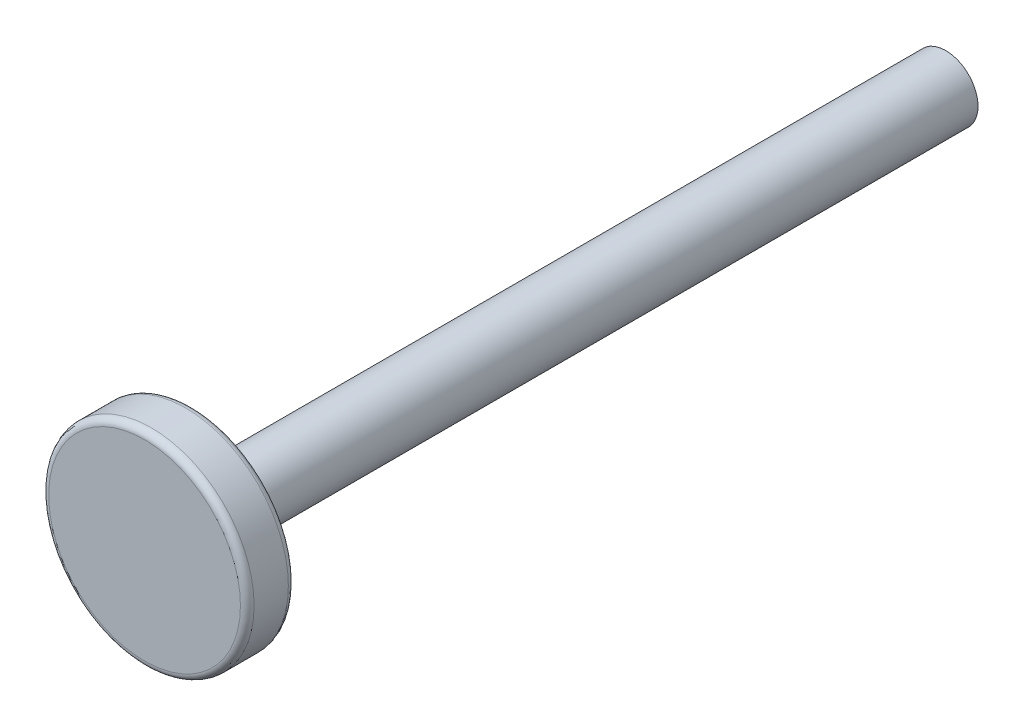
SolidWorks part; units mm, degrees
ref_plane "Front Plane" through (0, 0, 0) normal (0, 0, 1) x (1, 0, 0)
ref_plane "Top Plane" through (0, 0, 0) normal (0, 1, 0) x (1, 0, 0)
ref_plane "Right Plane" through (0, 0, 0) normal (1, 0, 0) x (0, 0, -1)
sketch "Sketch2" plane through (0, 0, 7.4325) normal (0, 0, 1) x (1, 0, 0)
  circle A0 centre (-105.394, 23.97) radius 2.35
  dimension "D1" = 4.7
extrude "Boss-Extrude1" add sketch "Sketch2" along normal blind 55
sketch "Sketch3" plane through (0, 0, 62.4325) normal (0, 0, 1) x (1, 0, 0)
  circle A0 centre (-105.394, 23.97) radius 7.5
  dimension "D1" = 15
extrude "Boss-Extrude2" add sketch "Sketch3" along normal blind 3.5
fillet "Fillet1" radius 0.5 3 edges at (-97.894, 23.97, 65.9325) (-97.894, 23.97, 62.4325) (-103.044, 23.97, 62.4325)
hole_wizard "M3x0.5 Tapped Hole1" positions "3DSketch1" profile "Sketch4" tap size "M3x0.5" standard "ANSI Metric"
sketch3d "3DSketch1"
  line L0 (-105.394, 23.97, 61.9325) -> (-105.394, 23.97, 7.4325) construction
  circle A0 centre (-105.394, 23.97, 7.4325) radius 1.9165
  point P0 (-105.394, 23.97, 7.4325)
  point P17 (-105.394, 23.97, 9.3491)
sketch "Sketch4" plane through (-105.394, 23.97, 7.4325) normal (1, 0, 0) x (0, 1, 0)
  line L0 (0, 0) -> (0, 20.7511)
  line L1 (0, 20.7511) -> (1.25, 20)
  line L2 (1.25, 20) -> (1.25, 0.275)
  line L3 (1.25, 0.275) -> (1.525, 0)
  line L5 (1.525, 0) -> (0, 0)
  line L6 (-1.25, 0.275) -> (-1.525, 0) construction
  line L10 (0, 20.7511) -> (-1.25, 20) construction
  line L11 (0, -6.35) -> (0, 107.95) construction
  dimension "Tap Drill Dia." = 2.5
  dimension "Tap Drill Depth" = 20
  dimension "Near C'Sink Dia." = 3.05
  dimension "Near C'Sink Angle" = 90
  dimension "Drill Angle" = 118
cosmetic thread "Hole Thread1" parameters "D1"=9.73, "D2"=3
ref_axis "Axis1" through (-105.394, 23.97, 61.9325) along (0, 0, -1)
